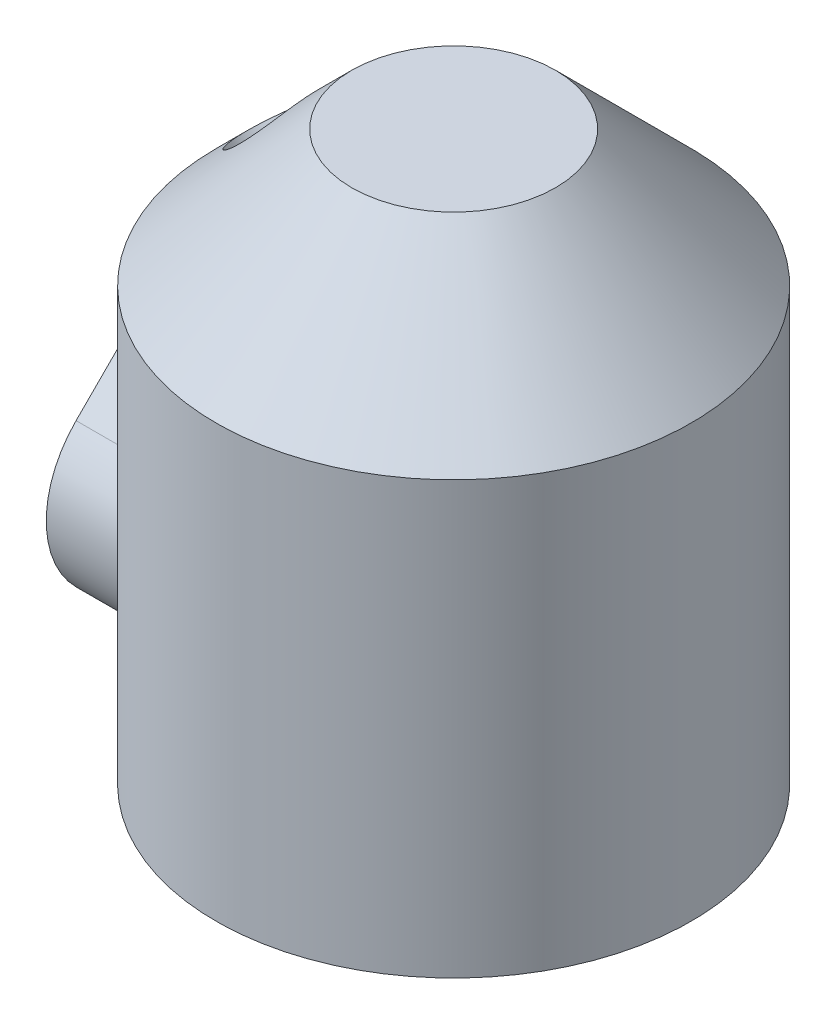
SolidWorks part; units mm, degrees
ref_plane "Front Plane" through (0, 0, 0) normal (0, 0, 1) x (1, 0, 0)
ref_plane "Top Plane" through (0, 0, 0) normal (0, 1, 0) x (1, 0, 0)
ref_plane "Right Plane" through (0, 0, 0) normal (1, 0, 0) x (0, 0, -1)
sketch "Sketch1" plane through (0, 0, 0) normal (0, 0, 1) x (1, 0, 0)
  line L4 (0, 0) -> (0, -29.6863)
  line L5 (0, -29.6863) -> (-3.81, -33.4963)
  line L6 (-3.81, -33.4963) -> (-3.81, -44.9263)
  line L7 (-3.81, -44.9263) -> (-2.54, -46.1963)
  line L8 (-2.54, -46.1963) -> (-2.54, -48.7363)
  line L9 (-2.54, -48.7363) -> (-3.3337, -48.7363)
  line L10 (-3.3337, -48.7363) -> (-3.3337, -46.525)
  line L11 (-3.3337, -46.525) -> (-4.6037, -45.255)
  line L12 (-4.6037, -45.255) -> (-4.6037, -40.7081)
  line L13 (-5.3975, -32.8387) -> (-1.5875, -29.0287)
  line L14 (-1.5875, -29.0287) -> (-1.5875, -6.35)
  line L15 (-1.5875, -6.35) -> (-19.05, -23.8125)
  line L16 (-19.05, -23.8125) -> (-5.3975, -37.465)
  line L17 (0, 0) -> (-9.525, 0)
  line L18 (-9.525, 0) -> (-22.225, -12.7)
  line L19 (-8.0391, -47.7157) -> (-17.0081, -56.6847)
  line L20 (-5.3975, -32.8387) -> (-5.3975, -37.465)
  line L21 (-4.6037, -40.7081) -> (-5.5277, -39.7842)
  line L22 (-5.5277, -39.7842) -> (-6.4516, -40.7081)
  line L23 (-6.4516, -40.7081) -> (-6.4516, -47.0581)
  line L24 (-6.4516, -47.0581) -> (-4.445, -49.0647)
  line L25 (-4.445, -49.0647) -> (-4.445, -56.6847)
  line L26 (-4.445, -56.6847) -> (-6.0325, -56.6847)
  line L27 (-6.0325, -56.6847) -> (-6.0325, -49.7223)
  line L28 (-6.0325, -49.7223) -> (-8.0391, -47.7157)
  line L29 (-8.0391, -45.4706) -> (-8.0391, -40.0506)
  line L30 (-8.0391, -40.0506) -> (-6.548, -38.5595)
  line L31 (-6.548, -38.5595) -> (-15.875, -29.2326)
  line L32 (-15.875, -29.2326) -> (-19.05, -32.4076)
  line L33 (-19.05, -32.4076) -> (-19.05, -52.3978)
  line L34 (-19.05, -52.3978) -> (-17.0081, -54.4397)
  line L35 (-17.0081, -54.4397) -> (-8.0391, -45.4706)
  line L36 (-17.0081, -56.6847) -> (-20.6375, -53.0554)
  line L37 (-20.6375, -53.0554) -> (-22.225, -53.0554)
  line L38 (-22.225, -53.0554) -> (-22.225, -12.7)
  line L39 (0, -29.6863) -> (0, -158.2007) construction
  line L40 (-2.54, -48.7363) -> (-4.445, -50.3347) construction
  line L41 (-6.4516, -40.7081) -> (-4.6037, -40.7081) construction
  line L42 (-19.05, -23.8125) -> (-19.05, -32.4076) construction
  line L43 (-17.0081, -56.6847) -> (-6.0325, -56.6847) construction
  dimension "D1" = 135
  dimension "D2" = 0.7937
  dimension "D3" = 0.7937
  dimension "D4" = 0.7937
  dimension "D5" = 1.5875
  dimension "D6" = 1.5875
  dimension "D7" = 1.5875
  dimension "D8" = 1.5875
  dimension "D9" = 1.5875
  dimension "D10" = 1.5875
  dimension "D11" = 1.5875
  dimension "D12" = 3.81
  dimension "D13" = 11.43
  dimension "D14" = 2.54
  dimension "D15" = 2.54
  dimension "D16" = 4.445
  dimension "D17" = 6.4516
  dimension "D18" = 6.35
  dimension "D19" = 7.62
  dimension "D20" = 19.05
  dimension "D23" = 6.35
  dimension "D24" = 1.5875
  dimension "D25" = 3.9688
  dimension "D21" = 19.05
  dimension "D22" = 135
  dimension "D27" = 1.5875
  dimension "D28" = 40
  dimension "D29" = 3.175
  dimension "D30" = 1.5875
  dimension "D31" = 4.7625
  dimension "D26" = 1.5875
  dimension "D32" = 3.175
  dimension "D33" = 6.35
  dimension "D34" = 9.525
revolve "Revolve1" add sketch "Sketch1" angle 360 about L39
ref_plane "Plane1" through (-22.225, 0, 0) normal (-1, 0, 0) x (0, 0, 1)
sketch "Sketch2" plane through (-22.225, 0, 0) normal (-1, 0, 0) x (0, 0, 1)
  line L0 (-6.7352, -34.5398) -> (-0.7938, -28.5984)
  line L1 (0.7937, -28.5984) -> (6.7352, -34.5398)
  line L2 (-0.7938, -28.5984) -> (-0.7938, -15.8984)
  line L3 (-0.7938, -15.8984) -> (0.7937, -15.8984)
  line L4 (0.7937, -15.8984) -> (0.7937, -28.5984)
  line L5 (-0.7938, -28.5984) -> (0.7937, -28.5984) construction
  line L6 (0, -28.5984) -> (0, -41.275) construction
  arc A0 (6.7352, -34.5398) -> (-6.7352, -34.5398) centre (0, -41.275) cw
  dimension "D4" = 9.525
  dimension "D1" = 12.7
  dimension "D2" = 90
  dimension "D3" = 1.5875
  dimension "D5" = 41.275
extrude "Boss-Extrude1" add sketch "Sketch2" along normal blind 6.35 and the other way up to surface other way up to face at (-22.225, -53.0554, 0)
sketch "Sketch3" plane through (0, 0, -0.7938) normal (0, 0, -1) x (-1, 0, 0)
  line L0 (28.575, -28.5984) -> (22.2108, -15.8984)
  line L1 (28.575, -15.8984) -> (22.2108, -15.8984) construction
  line L2 (22.2108, -15.8984) -> (28.575, -15.8984)
  line L3 (28.575, -15.8984) -> (28.575, -28.5984)
extrude "Cut-Extrude1" cut sketch "Sketch3" against normal through all
sketch "Sketch4" plane through (0, 0, 0) normal (0, 0, 1) x (1, 0, 0)
  line L0 (-3.2258, -33.4963) -> (-3.6389, -33.9093)
  line L1 (-2.8127, -33.9093) -> (-3.2258, -33.4963)
  line L2 (-3.2258, -34.3224) -> (-3.2258, -33.4963) construction
  line L3 (-3.81, -33.4963) -> (-3.81, -44.9263) construction
  line L4 (-5.5626, -40.7081) -> (-6.1912, -41.3368)
  line L5 (-4.934, -41.3368) -> (-5.5626, -40.7081)
  line L6 (-5.5626, -40.7081) -> (-5.5626, -41.9654) construction
  line L7 (-6.4516, -40.7081) -> (-6.4516, -47.0581) construction
  arc A0 (-3.6389, -33.9093) -> (-2.8127, -33.9093) centre (-3.2258, -34.3224) ccw
  arc A1 (-6.1912, -41.3368) -> (-4.934, -41.3368) centre (-5.5626, -41.9654) ccw
  point P4 (-3.81, -34.3224)
  point P5 (-2.6416, -34.3224)
  point P6 (-3.2258, -34.9066)
  point P11 (-6.4516, -41.9654)
  point P15 (-5.5626, -42.8544)
  point P16 (-4.6736, -41.9654)
  dimension "D2" = 0.5842
  dimension "D4" = 0.889
  dimension "D1" = 90
  dimension "D3" = 90
extrude "Cut-Extrude2" cut sketch "Sketch4" against normal up to next
pattern_circular "CirPattern1" count 6 over 360 about axis through (0, -29.6863, 0) along (0, -1, 0) of "Cut-Extrude2"
ref_axis "Axis1" through (0, -166.1108, 0) along (0, 1, 0)
ref_axis "Axis2" through (25.0825, 0, 0) along (-1, 0, 0)
ref_axis "Axis3" through (0, 0, -24.4475) along (0, 0, 1)
hole_wizard "1/8 NPT Tapped Hole1" positions "Sketch5" profile "Sketch6" size "1/8" standard "ANSI Inch"
sketch "Sketch5" plane through (-28.575, 0, 0) normal (-1, 0, 0) x (0, 0, 1)
  point P0 (0, -41.275)
sketch "Sketch6" plane through (-28.575, -41.275, 0) normal (0, 1, 0) x (0, 0, 1)
  line L0 (0, 0) -> (0, 14.2175)
  line L1 (4.2164, 11.684) -> (0, 14.2175)
  line L2 (-4.2164, 11.684) -> (0, 14.2175) construction
  line L3 (4.2164, 11.684) -> (4.2164, 6.858)
  line L4 (4.2164, 6.858) -> (4.5374, 6.858)
  line L5 (4.5374, 6.858) -> (4.7427, 0)
  line L6 (-4.5374, 6.858) -> (-4.7427, 0) construction
  line L7 (4.7427, 0) -> (0, 0)
  line L8 (0, -6.35) -> (0, 107.95) construction
  line L11 (-4.2164, 6.858) -> (-4.5374, 6.858) construction
  dimension "Tap Drill Dia." = 8.4328
  dimension "Tap Drill Depth" = 11.684
  dimension "Thread Dia." = 9.4855
  dimension "Thread Angle" = 3.43
  dimension "Thread Depth" = 6.858
  dimension "Drill Angle" = 118
cosmetic thread "Hole Thread1" parameters "D1"=6.858, "D2"=10.2827
ref_plane "Plane2" through (-4.7625, 4.7625, 0) normal (-0.7071, 0.7071, 0) x (0, 0, 1)
hole_wizard "1/8 NPT Tapped Hole3" positions "Sketch9" profile "Sketch10" size "1/8" standard "ANSI Inch"
sketch "Sketch9" plane through (-4.7625, 4.7625, 0) normal (-0.7071, 0.7071, 0) x (0, 0, 1)
  line L0 (0, 0) -> (0, -20.9913) construction
  point P0 (0, -15.875)
  dimension "D1" = 15.875
sketch "Sketch10" plane through (-15.9878, -6.4628, 0) normal (0, 0, 1) x (-0.7071, -0.7071, 0)
  line L0 (0, 0) -> (0, 14.2175)
  line L1 (4.2164, 11.684) -> (0, 14.2175)
  line L2 (-4.2164, 11.684) -> (0, 14.2175) construction
  line L3 (4.2164, 11.684) -> (4.2164, 6.858)
  line L4 (4.2164, 6.858) -> (4.5374, 6.858)
  line L5 (4.5374, 6.858) -> (4.7427, 0)
  line L6 (-4.5374, 6.858) -> (-4.7427, 0) construction
  line L7 (4.7427, 0) -> (0, 0)
  line L8 (0, -6.35) -> (0, 107.95) construction
  line L11 (-4.2164, 6.858) -> (-4.5374, 6.858) construction
  dimension "Tap Drill Dia." = 8.4328
  dimension "Tap Drill Depth" = 11.684
  dimension "Thread Dia." = 9.4855
  dimension "Thread Angle" = 3.43
  dimension "Thread Depth" = 6.858
  dimension "Drill Angle" = 118
cosmetic thread "Hole Thread3" parameters "D1"=6.858, "D2"=10.2827
equation "\"w_t1\"= 0.03125"
equation "\"w_t2\"= 0.0625"
equation "\"n_1\"= 6"
equation "\"n_2\"= 6"
equation "\"R_n1\"= .1"
equation "\"R_n2\"= .175"
equation "\"l_n1\"= .1"
equation "\"l_n2\"=0.3"
equation "\"D2@Sketch1\"=\"w_t1\""
equation "\"D3@Sketch1\"=\"w_t1\""
equation "\"D4@Sketch1\"=\"w_t1\""
equation "\"D5@Sketch1\"=\"w_t2\""
equation "\"D6@Sketch1\"=\"w_t2\""
equation "\"D7@Sketch1\"=\"w_t2\""
equation "\"D8@Sketch1\"=\"w_t2\""
equation "\"D9@Sketch1\"=\"w_t2\""
equation "\"D10@Sketch1\"=\"w_t2\""
equation "\"R_s1\"= .15"
equation "\"R_s2\"= .254"
equation "\"l_s1\"=0.45"
equation "\"l_s2\"= .25"
equation "\"r_in1\"= .023"
equation "\"r_in2\"= .035"
equation "\"D12@Sketch1\"=\"R_s1\""
equation "\"D13@Sketch1\"=\"l_s1\""
equation "\"D14@Sketch1\"=\"R_n1\""
equation "\"D15@Sketch1\"=\"l_n1\""
equation "\"D16@Sketch1\"=\"R_n2\""
equation "\"D17@Sketch1\"=\"R_s2\""
equation "\"D18@Sketch1\"=\"l_s2\""
equation "\"D19@Sketch1\"=\"l_n2\""
equation "\"D2@Sketch4\"=\"r_in1\""
equation "\"D4@Sketch4\"=\"r_in2\""
equation "\"D1@CirPattern1\"=\"n_2\""
